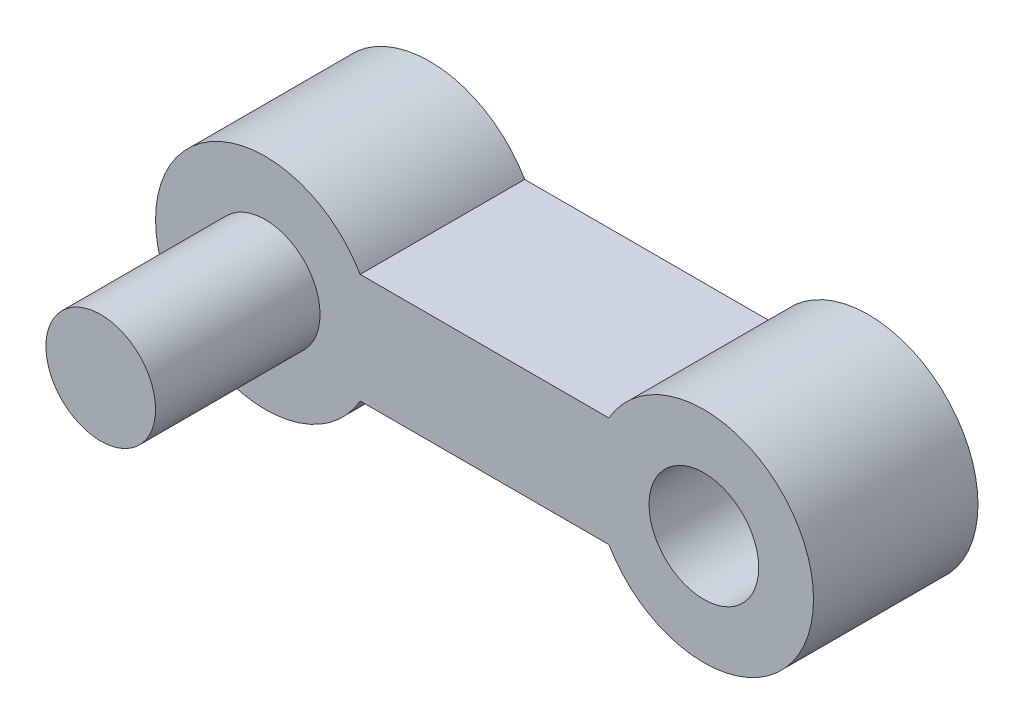
SolidWorks part; units mm, degrees
ref_plane "Спереди" through (0, 0, 0) normal (0, 0, 1) x (1, 0, 0)
ref_plane "Сверху" through (0, 0, 0) normal (0, 1, 0) x (1, 0, 0)
ref_plane "Справа" through (0, 0, 0) normal (1, 0, 0) x (0, 0, -1)
other "Configuration Table"
sketch "Sketch2" plane through (0, 0, 0) normal (0, 0, 1) x (1, 0, 0)
  line L1 (-36.505, 13.8003) -> (-31.9691, 13.8003)
  line L5 (-36.505, 11.8003) -> (-31.9691, 11.8003)
  line L7 (-13.5959, 12.8003) -> (-45.3291, 12.8003) construction
  arc A0 (-36.505, 13.8003) -> (-36.505, 11.8003) centre (-38.2371, 12.8003) ccw
  arc A2 (-31.9691, 13.8003) -> (-31.9691, 11.8003) centre (-30.2371, 12.8003) cw
  arc A3 (-36.505, 11.8003) -> (-36.2371, 12.8003) centre (-38.2371, 12.8003) ccw construction
  arc A4 (-36.2371, 12.8003) -> (-36.505, 13.8003) centre (-38.2371, 12.8003) ccw construction
  arc A5 (-31.9691, 11.8003) -> (-32.2371, 12.8003) centre (-30.2371, 12.8003) cw construction
  arc A6 (-32.2371, 12.8003) -> (-31.8371, 14.0003) centre (-30.2371, 12.8003) cw construction
  dimension "D3" = 4
  dimension "D1" = 2
  dimension "D2" = 8
extrude "Boss-Extrude1" add sketch "Sketch2" along normal blind 3 contours L1 A0 | A2 L1 A0 | A2 L1 | A0 | A2 region at (-34.2371, 12.8003, 0)
ref_plane "Plane1" through (0, 0, 3) normal (0, 0, 1) x (1, 0, 0)
sketch "Sketch3" plane through (0, 0, 3) normal (0, 0, 1) x (1, 0, 0)
  circle A0 centre (-38.2371, 12.8003) radius 1
  dimension "D1" = 2
extrude "Boss-Extrude2" add sketch "Sketch3" along normal blind 3
ref_plane "Plane2" through (0, 0, 0) normal (0, 0, -1) x (-1, 0, 0)
sketch "Sketch4" plane through (0, 0, 0) normal (0, 0, -1) x (-1, 0, 0)
  circle A0 centre (30.2371, 12.8003) radius 1
  circle A1 centre (38.2371, 12.8003) radius 1 construction
extrude "Cut-Extrude1" cut sketch "Sketch4" against normal up to surface (3 mm away) up to face at (-37.2371, 12.8003, 3)
equation "\"R small\"= 2"
equation "\"R big\"= 4"
equation "\"width\"= 0.6"
equation "\"border width\"= 1"
equation "\"D3@Sketch2\"=\"R big\""
equation "\"D1@Sketch2\"=\"R small\""
equation "\"D1@Sketch3\"=\"R small\""
